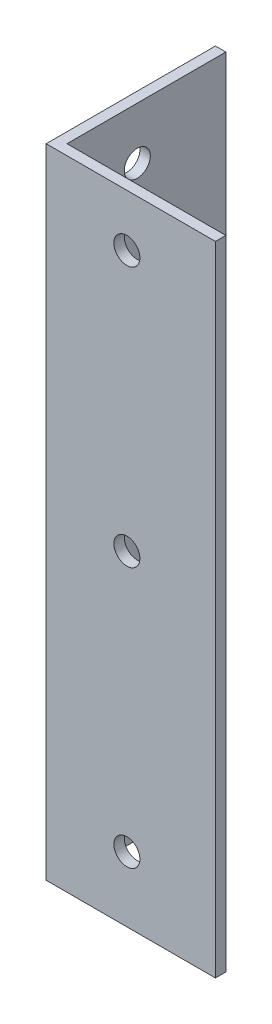
SolidWorks part; units mm, degrees
ref_plane "Спереди" through (0, 0, 0) normal (0, 0, 1) x (1, 0, 0)
ref_plane "Сверху" through (0, 0, 0) normal (0, 1, 0) x (1, 0, 0)
ref_plane "Справа" through (0, 0, 0) normal (1, 0, 0) x (0, 0, -1)
sketch "Эскиз1" plane through (0, 0, 0) normal (0, 1, 0) x (1, 0, 0)
  line L0 (0, 0) -> (65, 0)
  line L1 (0, 0) -> (0, 65)
extrude "Вытянуть-Тонкостенный1" add sketch "Эскиз1" along normal blind 245 thin thin type one direction wall 4
sketch "Эскиз2" plane through (0, 0, 0) normal (0, 0, 1) x (1, 0, 0)
  circle A0 centre (31, 225) radius 5
  circle A1 centre (31, 125) radius 5
  circle A2 centre (31, 25) radius 5
  dimension "D1" = 3
extrude "Вырез-Вытянуть1" cut sketch "Эскиз2" against normal blind 10
sketch "Эскиз3" plane through (0, 0, 0) normal (-1, 0, 0) x (0, 0, 1)
  circle A0 centre (-31, 225) radius 5
  circle A1 centre (-31, 125) radius 5
  circle A2 centre (-31, 25) radius 5
  dimension "D1" = 3
extrude "Вырез-Вытянуть2" cut sketch "Эскиз3" against normal blind 10
